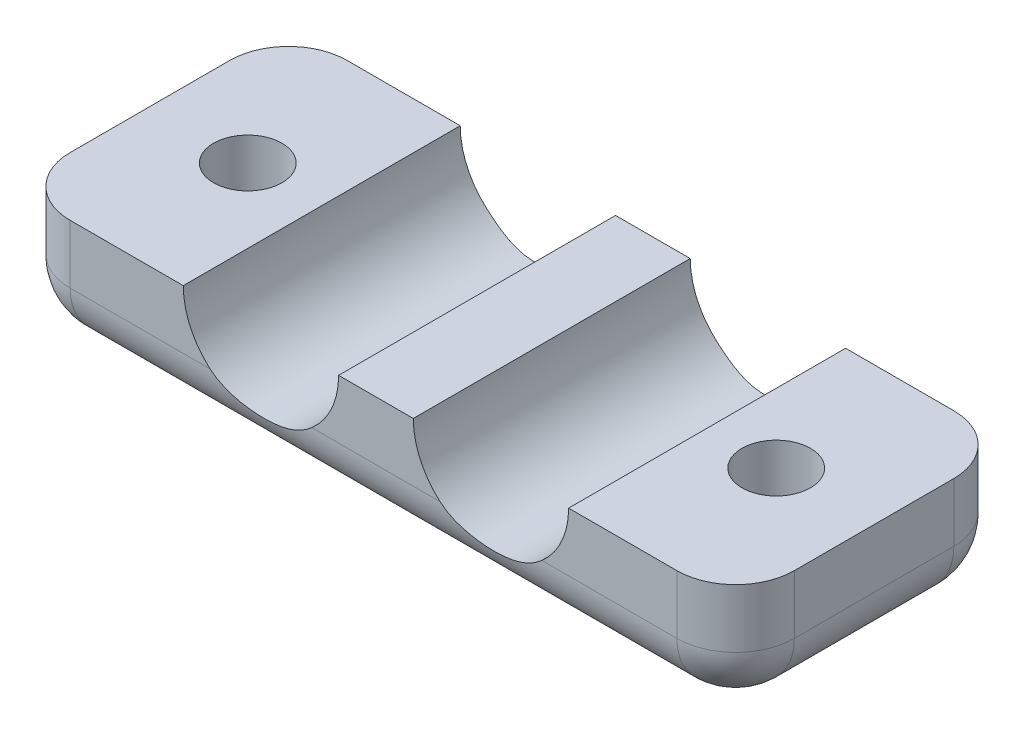
SolidWorks part; units mm, degrees
material "ABS"
ref_plane "Plano frontal" through (0, 0, 0) normal (0, 0, 1) x (1, 0, 0)
ref_plane "Plano superior" through (0, 0, 0) normal (0, 1, 0) x (1, 0, 0)
ref_plane "Plano direito" through (0, 0, 0) normal (1, 0, 0) x (0, 0, -1)
sketch "Esboço1" plane through (0, 0, 0) normal (0, 0, 1) x (1, 0, 0)
  line L0 (18.5, 0) -> (-18.5, 0)
  line L1 (18.5, 0) -> (18.5, -6)
  line L2 (18.5, -6) -> (-18.5, -6)
  line L3 (-18.5, -6) -> (-18.5, 0)
  line L4 (18.5, -3) -> (13.5, -3) construction
  line L5 (13.5, -3) -> (7, -3) construction
  line L7 (-7, -3) -> (-13.5, -3) construction
  line L8 (-13.5, -3) -> (-18.5, -3) construction
extrude "Ressalto-extrusão1" add sketch "Esboço1" along normal blind 14.15 contours L0 L3 L2 L1
sketch "Esboço2" plane through (0, 0, 0) normal (0, 0, -1) x (-1, 0, 0)
  line L0 (-18.5, 0) -> (-12.5, 0) construction
  line L1 (-18.5, 0) -> (18.5, 0) construction
  line L2 (-12.5, 0) -> (-6, 0) construction
  line L3 (-6, 0) -> (5.7529, 0) construction
  line L4 (5.7529, 0) -> (12.5, 0) construction
  line L5 (12.5, 0) -> (18.5, 0) construction
  circle A0 centre (-6, 0) radius 3.9688
  circle A1 centre (5.7529, 0) radius 3.9688
extrude "Corte-extrusão1" cut sketch "Esboço2" against normal through all
sketch "Esboço3" plane through (0, -6, 0) normal (0, -1, 0) x (1, 0, 0)
  line L0 (-18.5, 7.075) -> (-13.5, 7.075) construction
  line L1 (-18.5, 14.15) -> (-18.5, 0) construction
  line L2 (-13.5, 7.075) -> (13.5, 7.075) construction
  line L3 (13.5, 7.075) -> (18.5, 7.075) construction
  line L4 (18.5, 14.15) -> (18.5, 0) construction
  circle A0 centre (-13.5, 7.075) radius 1.75
  circle A1 centre (13.5, 7.075) radius 1.75
extrude "Corte-extrusão2" cut sketch "Esboço3" against normal blind 13
fillet "Filete2" radius 3 4 edges at (-18.5, -6, 7.075) (0, -6, 14.15) (0, -6, 0) (18.5, -6, 7.075)
fillet "Filete3" radius 3 8 edges at (-17.6213, -5.1213, 13.2713) (17.6213, -5.1213, 13.2713) (17.6213, -5.1213, 0.8787) (-17.6213, -5.1213, 0.8787) (-18.5, -1.5, 14.15) (18.5, -1.5, 14.15) (18.5, -1.5, 0) (-18.5, -1.5, 0)
